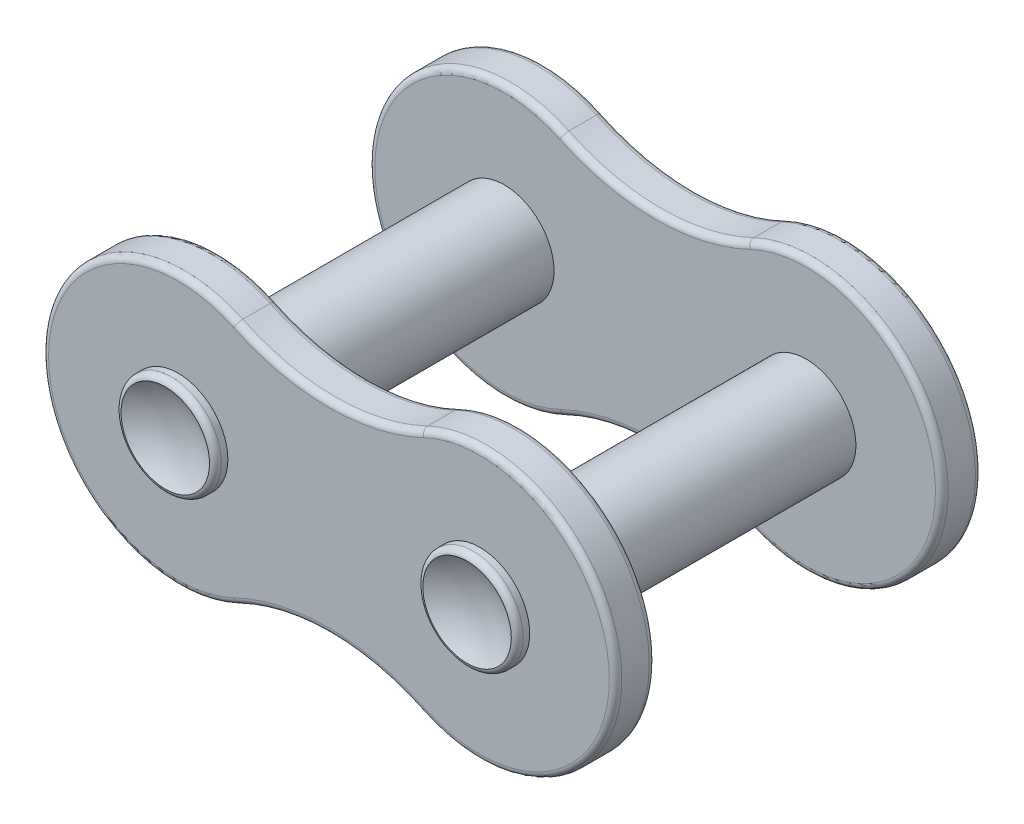
SolidWorks part; units mm, degrees
other "Câmera1"
ref_plane "Plano frontal" through (0, 0, 0) normal (0, 0, 1) x (1, 0, 0)
ref_plane "Plano superior" through (0, 0, 0) normal (0, 1, 0) x (1, 0, 0)
ref_plane "Plano direito" through (0, 0, 0) normal (1, 0, 0) x (0, 0, -1)
sketch "Esboço1" plane through (0, 0, 0) normal (0, 0, 1) x (1, 0, 0)
  line L0 (0, 3.2803) -> (0, 0) construction
  line L1 (0, 0) -> (-6, 0) construction
  arc A0 (-3.6763, 4.8717) -> (-3.6763, -4.8717) centre (-6, 0) ccw
  circle A1 centre (-6, 0) radius 1.9812
  arc A2 (3.6763, 4.8717) -> (3.6763, -4.8717) centre (6, 0) cw
  circle A3 centre (6, 0) radius 1.9812
  arc A4 (-3.6763, 4.8717) -> (3.6763, 4.8717) centre (0, 12.5793) ccw
  arc A5 (-3.6763, -4.8717) -> (3.6763, -4.8717) centre (0, -12.5793) cw
  dimension "D1" = 10.795
  dimension "D2" = 3.9624
  dimension "D4" = 8.5395
  dimension "D3" = 6
extrude "Ressalto-extrusão1" add sketch "Esboço1" along normal blind 1.5875
sketch "Esboço2" plane through (0, 0, 0) normal (0, 0, 1) x (1, 0, 0)
  circle A0 centre (-6, 0) radius 1.9812 construction
  circle A1 centre (-6, 0) radius 1.9812
extrude "Ressalto-extrusão2" add sketch "Esboço2" along normal blind 15.0652 and the other way blind 0.508
ref_plane "Plano1" through (0, 0, 7.2786) normal (0, 0, 1) x (1, 0, 0)
mirror "Espelhar1" about plane through (0, 0, 7.2786) normal (0, 0, 1) of "Ressalto-extrusão1"
sketch "Esboço3" plane through (0, 0, 0) normal (0, 1, 0) x (1, 0, 0)
  line L0 (-6, -14.5572) -> (-6, -19.0254) construction
  line L1 (-7.9812, -14.5572) -> (-4.0188, -14.5572) construction
  line L2 (-6, -14.5572) -> (-6, -15.3192)
  line L3 (-6, -15.3192) -> (-8.1099, -15.3192)
  arc A2 (-8.1099, -15.3192) -> (-6, -14.5572) centre (-6, -17.8592) cw
  dimension "D2" = 3.302
  dimension "D1" = 0.762
revolve "Corte-Revolução1" cut sketch "Esboço3" angle 360 about L0
mirror "Espelhar2" about plane through (0, 0, 7.2786) normal (0, 0, 1) of "Corte-Revolução1"
mirror "Espelhar3" about plane through (0, 0, 0) normal (1, 0, 0) of "Espelhar2", "Corte-Revolução1", "Ressalto-extrusão2"
fillet "Filete1" radius 0.25 16 edges at (0, -4.0398, 0) (-11.3975, 0, 0) (0, 4.0398, 0) (0, -4.0398, 1.5875) (-11.3975, 0, 1.5875) (0, 4.0398, 1.5875) (0, -4.0398, 12.9697) (-11.3975, 0, 12.9697) (0, 4.0398, 12.9697) (0, -4.0398, 14.5572) (-11.3975, 0, 14.5572) (0, 4.0398, 14.5572) (11.3975, 0, 0) (11.3975, 0, 1.5875) (11.3975, 0, 12.9697) (11.3975, 0, 14.5572)
fillet "Filete2" radius 0.25 4 edges at (-4.0188, 0, -0.508) (4.0188, 0, -0.508) (-4.0188, 0, 15.0652) (4.0188, 0, 15.0652)
